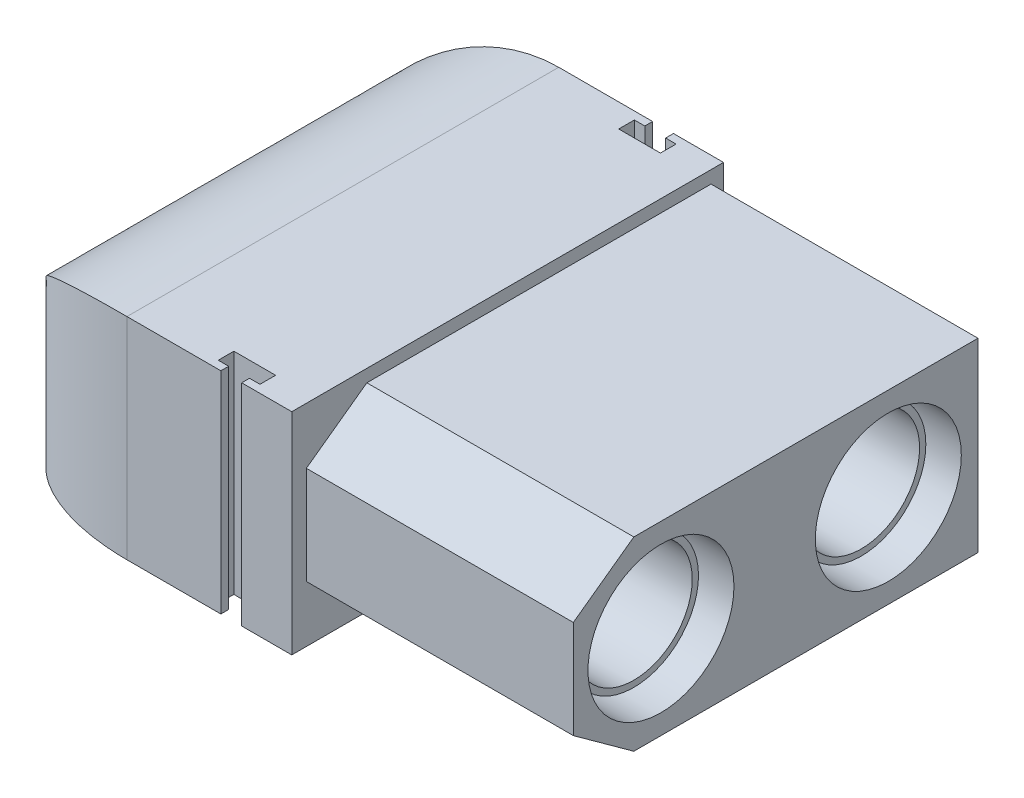
SolidWorks part; units mm, degrees
ref_plane "Front Plane" through (0, 0, 0) normal (0, 0, 1) x (1, 0, 0)
ref_plane "Top Plane" through (0, 0, 0) normal (0, 1, 0) x (1, 0, 0)
ref_plane "Right Plane" through (0, 0, 0) normal (1, 0, 0) x (0, 0, -1)
sketch "Sketch1" plane through (0, 0, 0) normal (0, 1, 0) x (1, 0, 0)
  line L0 (-7.1, 10.35) -> (-7.1, -10.35)
  line L1 (-13.6, 10.35) -> (-2.6, 10.35)
  line L2 (-13.6, 10.35) -> (-13.6, -10.35)
  line L3 (-13.6, -10.35) -> (-2.6, -10.35)
  line L4 (13.6, 10.35) -> (13.6, -10.35)
  line L5 (-13.6, 10.35) -> (13.6, -10.35) construction
  line L6 (-13.6, -10.35) -> (13.6, 10.35) construction
  line L7 (-7.1, -9.6) -> (-2.1, -9.6) construction
  line L8 (-2.1, -9.975) -> (-2.1, -10.35) construction
  line L9 (-3.1, -9.225) -> (-1.1, -9.225)
  line L10 (-3.1, -9.225) -> (-3.1, -9.975)
  line L11 (-3.1, -9.975) -> (-2.6, -9.975)
  line L12 (-1.1, -9.225) -> (-1.1, -9.975)
  line L13 (-3.1, -9.225) -> (-1.1, -9.975) construction
  line L14 (-3.1, -9.975) -> (-1.1, -9.225) construction
  line L15 (-2.6, -9.975) -> (-2.6, -10.35)
  line L16 (-1.6, -9.975) -> (-1.6, -10.35)
  line L17 (-1.6, -9.975) -> (-1.1, -9.975)
  line L18 (-1.6, -10.35) -> (13.6, -10.35)
  line L19 (13.6, 0) -> (-13.6, 0) construction
  line L20 (-2.6, 9.975) -> (-2.6, 10.35)
  line L21 (-3.1, 9.975) -> (-2.6, 9.975)
  line L22 (-3.1, 9.225) -> (-3.1, 9.975)
  line L23 (-3.1, 9.225) -> (-1.1, 9.225)
  line L24 (-1.1, 9.225) -> (-1.1, 9.975)
  line L25 (-1.6, 9.975) -> (-1.1, 9.975)
  line L26 (-1.6, 9.975) -> (-1.6, 10.35)
  line L27 (-1.6, 10.35) -> (13.6, 10.35)
  point P0 (0, 0)
  dimension "D1" = 27.2
  dimension "D2" = 20.7
  dimension "D3" = 20.7
  dimension "D4" = 5
  dimension "D5" = 2
  dimension "D6" = 0.75
  dimension "D7" = 0.75
  dimension "D8" = 0.5
  dimension "D9" = 0.5
extrude "Boss-Extrude1" add sketch "Sketch1" along normal blind 10.1 contours L27 L26 L25 L24 L23 L22 L21 L20 L1 L0 L3 L15 L11 L10 L9 L12 L17 L16 L18 L4 | L2 L3 L0 L1
fillet "Fillet1" radius 4 1 edges at (-13.6, 10.1, 0)
fillet "Fillet2" radius 6.5 2 edges
sketch "Sketch4" plane through (0, 0, 0) normal (0, -1, 0) x (1, 0, 0)
  line L0 (-13.6, -6.85) -> (-13.6, 6.85) construction
  line L1 (-7.1, -10.35) -> (-2.6, -10.35) construction
  line L2 (-7.1, 10.35) -> (-2.6, 10.35) construction
  circle A0 centre (-11.1, -5.65) radius 1.75
  circle A1 centre (-11.1, 5.65) radius 1.75
  point P8 (0, 0)
  point P10 (-11.2773, 4.4619)
  dimension "D1" = 3.5
  dimension "D4" = 3.5
  dimension "D2" = 2.5
  dimension "D3" = 4.7
  dimension "D5" = 2.5
  dimension "D6" = 4.7
extrude "Boss-Extrude3" add sketch "Sketch4" along normal blind 2.7
fillet "Fillet4" radius 0.15 2 edges at (-11.1, -2.7, -7.4) (-11.1, -2.7, 3.9)
sketch "Sketch2" plane through (13.6, 0, 0) normal (1, 0, 0) x (0, 0, -1)
  line L0 (-9.65, 7.4) -> (-9.65, 2.7)
  line L1 (-6.75, 0.6) -> (6.85, 0.6)
  line L2 (9.75, 2.7) -> (9.75, 7.4)
  line L3 (6.85, 9.5) -> (-6.75, 9.5)
  line L4 (-10.35, 0) -> (10.35, 0)
  line L5 (10.35, 0) -> (10.35, 10.1)
  line L6 (10.35, 10.1) -> (-10.35, 10.1)
  line L7 (-10.35, 10.1) -> (-10.35, 0)
  line L8 (-10.35, 0) -> (10.35, 0) construction
  line L9 (10.35, 0) -> (10.35, 10.1) construction
  line L10 (10.35, 10.1) -> (-10.35, 10.1) construction
  line L11 (-10.35, 10.1) -> (-10.35, 0) construction
  line L12 (9.75, 9.5) -> (-10.35, 9.5) construction
  line L13 (-9.65, 10.1) -> (-9.65, 0) construction
  line L14 (-10.35, 0.6) -> (9.75, 0.6) construction
  line L16 (-9.65, 5.05) -> (9.75, 5.05) construction
  line L18 (9.75, 0.6) -> (9.75, 9.5) construction
  line L19 (-6.75, 0.6) -> (-9.65, 2.7)
  line L20 (0.05, 0.6) -> (0.05, 9.5) construction
  line L21 (-6.75, 9.5) -> (-9.65, 7.4)
  line L22 (6.85, 9.5) -> (9.75, 9.5)
  line L23 (9.75, 9.5) -> (9.75, 0.6)
  line L24 (9.75, 0.6) -> (6.85, 0.6)
  dimension "D4" = 2.7
  dimension "D5" = 3.5
  dimension "D1" = 0
  dimension "D2" = 0.7
  dimension "D3" = 0.6
extrude "Cut-Extrude1" cut sketch "Sketch2" against normal blind 12.8
sketch "Sketch5" plane through (13.6, 0, 0) normal (1, 0, 0) x (0, 0, -1)
  line L0 (-9.65, 5.05) -> (9.75, 5.05) construction
  line L1 (-9.65, 7.4) -> (-9.65, 2.7) construction
  line L2 (9.75, 9.5) -> (9.75, 0.6) construction
  line L4 (-9.65, 7.4) -> (-9.65, 2.7) construction
  circle A0 centre (-5.45, 5.05) radius 3.5
  circle A1 centre (5.45, 5.05) radius 3.5
  dimension "D1" = 7
  dimension "D2" = 7
  dimension "D3" = 4.3
  dimension "D4" = 4.2
extrude "Cut-Extrude2" cut sketch "Sketch5" against normal blind 13.3
sketch "Sketch6" plane through (0.3, 0, 0) normal (1, 0, 0) x (0, 0, -1)
  circle A0 centre (5.45, 5.05) radius 3.5 construction
  circle A1 centre (-5.45, 5.05) radius 3.5 construction
  circle A2 centre (5.45, 5.05) radius 3.5 construction
  circle A3 centre (-5.45, 5.05) radius 3.5 construction
  circle A4 centre (-5.45, 5.05) radius 3.1
  circle A5 centre (5.45, 5.05) radius 3.1
  circle A6 centre (5.45, 5.05) radius 2.8
  circle A7 centre (-5.45, 5.05) radius 2.8
  dimension "D2" = 0.3
  dimension "D1" = 0.4
extrude "Boss-Extrude4" add sketch "Sketch6" along normal blind 12
